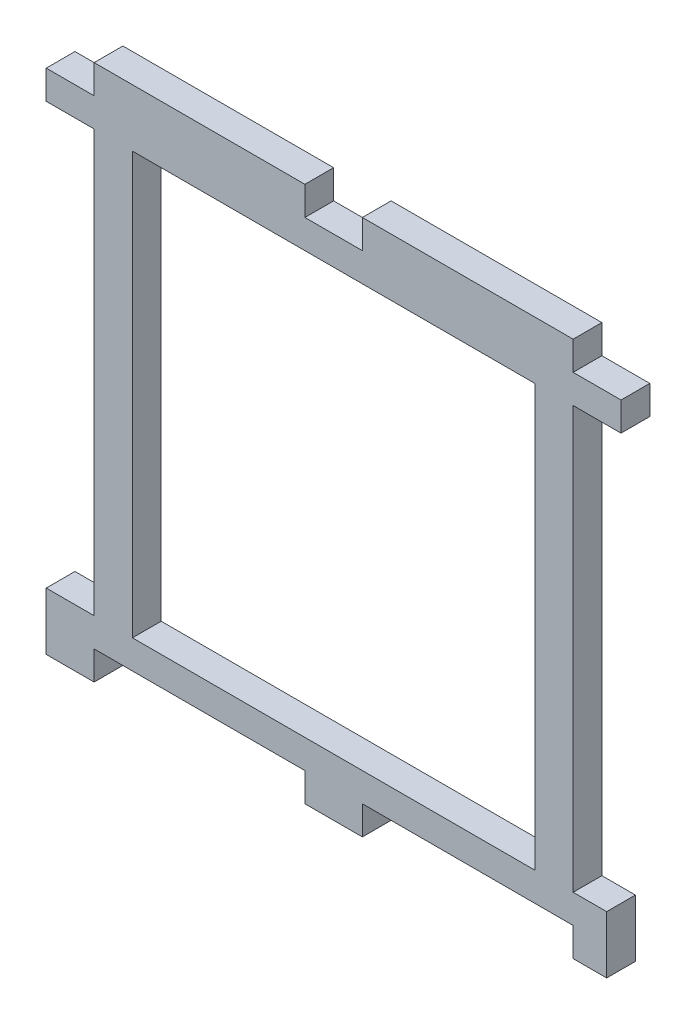
SolidWorks part; units mm, degrees
material "Custom Plastic"
ref_plane "Front Plane" through (0, 0, 0) normal (0, 0, 1) x (1, 0, 0)
ref_plane "Top Plane" through (0, 0, 0) normal (0, 1, 0) x (1, 0, 0)
ref_plane "Right Plane" through (0, 0, 0) normal (1, 0, 0) x (0, 0, -1)
sketch "Sketch1" plane through (0, 0, 0) normal (0, 0, 1) x (1, 0, 0)
  line L46 (0, 0) -> (5, 0)
  line L47 (5, 0) -> (5, 3)
  line L48 (5, 3) -> (27, 3)
  line L49 (27, 3) -> (27, 0)
  line L50 (27, 0) -> (33, 0)
  line L51 (33, 0) -> (33, 3)
  line L52 (33, 3) -> (55, 3)
  line L53 (55, 3) -> (55, 0)
  line L54 (55, 0) -> (60, 0)
  line L55 (60, 0) -> (60, -3)
  line L56 (60, -3) -> (55, -3)
  line L57 (55, -3) -> (55, -47)
  line L58 (55, -47) -> (58.5, -47)
  line L59 (58.5, -47) -> (58.5, -53)
  line L60 (58.5, -53) -> (55, -53)
  line L61 (55, -53) -> (55, -50)
  line L62 (55, -50) -> (33, -50)
  line L63 (33, -50) -> (33, -53)
  line L64 (33, -53) -> (27, -53)
  line L65 (27, -53) -> (27, -50)
  line L66 (27, -50) -> (5, -50)
  line L67 (5, -50) -> (5, -53)
  line L68 (5, -53) -> (0, -53)
  line L69 (0, -53) -> (0, -47)
  line L70 (0, -47) -> (5, -47)
  line L71 (0, 0) -> (0, -3)
  line L72 (0, -3) -> (5, -3)
  line L73 (5, -3) -> (5, -47)
  line L74 (9, -3) -> (9, -47)
  line L75 (9, -47) -> (51, -47)
  line L76 (51, -47) -> (51, -3)
  line L77 (51, -3) -> (9, -3)
  dimension "D10" = 5
  dimension "D11" = 3
  dimension "D12" = 22
  dimension "D13" = 6
  dimension "D14" = 22
  dimension "D15" = 5
  dimension "D16" = 3
  dimension "D17" = 44
  dimension "D18" = 6
  dimension "D19" = 3.5
  dimension "D20" = 3
  dimension "D21" = 22
  dimension "D22" = 6
  dimension "D23" = 4
  dimension "D24" = 4
extrude "Boss-Extrude1" add sketch "Sketch1" along normal blind 3
